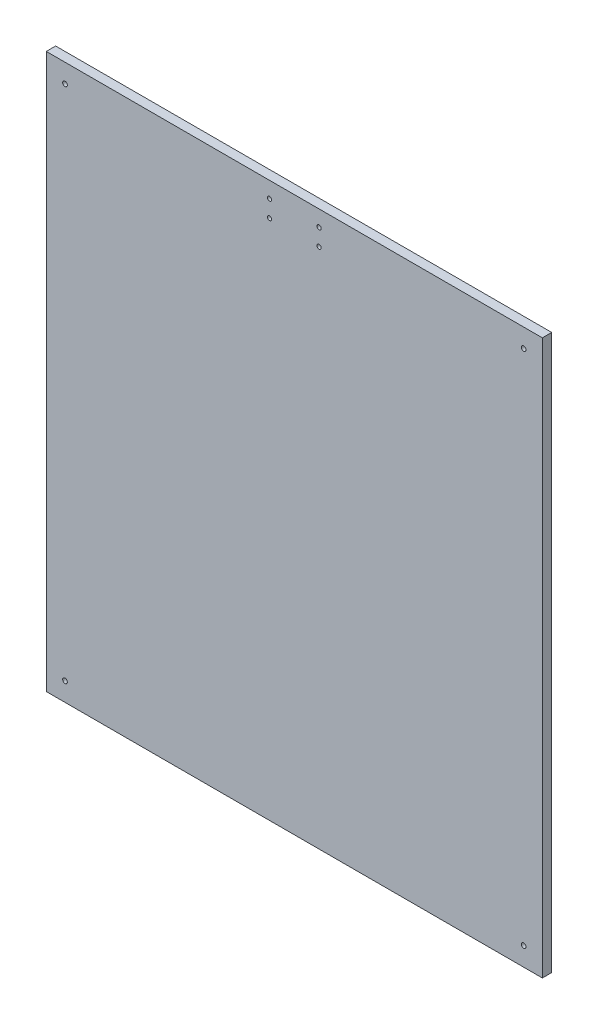
SolidWorks part; units mm, degrees
ref_plane "Спереди" through (0, 0, 0) normal (0, 0, 1) x (1, 0, 0)
ref_plane "Сверху" through (0, 0, 0) normal (0, 1, 0) x (1, 0, 0)
ref_plane "Справа" through (0, 0, 0) normal (1, 0, 0) x (0, 0, -1)
sketch "Эскиз3" plane through (0, 0, 0) normal (0, 0, 1) x (1, 0, 0)
  line L5 (265, -296.15) -> (-265, -296.15)
  line L6 (265, -296.15) -> (265, 296.15)
  line L7 (265, 296.15) -> (-265, 296.15)
  line L8 (-265, -296.15) -> (-265, 296.15)
  point P0 (0, 0)
  point P5 (-265, 0)
  point P6 (0, 296.15)
  dimension "D1" = 592.3
  dimension "D2" = 530
extrude "Бобышка-Вытянуть1" add sketch "Эскиз3" along normal blind 10
sketch "Эскиз4" plane through (0, 0, 10) normal (0, 0, 1) x (1, 0, 0)
  line L0 (265, 296.15) -> (-265, 296.15) construction
  line L1 (-265, 296.15) -> (-265, -296.15) construction
  circle A0 centre (-245, 276.15) radius 2.5
  dimension "D1" = 5
  dimension "D2" = 20
  dimension "D3" = 20
extrude "Вырез-Вытянуть1" cut sketch "Эскиз4" against normal through all contours A0
pattern_linear "Линейный массив1" count 2 spacing 490 along (1, 0, 0) count 2 spacing 552.3 along (0, -1, 0) of "Вырез-Вытянуть1"
sketch "Эскиз7" plane through (0, 0, 0) normal (0, 0, -1) x (-1, 0, 0)
  line L9 (-26.5, 279.15) -> (26.5, 279.15) construction
  line L10 (-26.5, 279.15) -> (-26.5, 261.15) construction
  line L11 (-26.5, 261.15) -> (26.5, 261.15) construction
  line L16 (26.5, 279.15) -> (26.5, 261.15) construction
  line L17 (-265, 296.15) -> (265, 296.15) construction
  circle A0 centre (-26.5, 279.15) radius 2.25
  circle A1 centre (26.5, 279.15) radius 2.25
  circle A2 centre (-26.5, 261.15) radius 2.25
  circle A3 centre (26.5, 261.15) radius 2.25
  point P4 (0, 261.15)
  dimension "D4" = 4.5
  dimension "D5" = 4.5
  dimension "D6" = 4.5
  dimension "D7" = 4.5
  dimension "D1" = 53
  dimension "D2" = 18
  dimension "D3" = 17
extrude "Вырез-Вытянуть2" cut sketch "Эскиз7" against normal through all
equation "\"Ширина груза\"= 420"
equation "\"Глубина груза\"= 490"
equation "\"Высота груза\"= 297"
equation "\"Ширина ячейки\"= \"Ширина груза\" + 10"
equation "\"Глубина ячейки\"= \"Глубина груза\" + 10"
equation "\"Высота ячейки\"= \"Высота груза\" + 10 + 13"
equation "\"Колво ячеек ширина\"= 2"
equation "\"Колво ячеек высота\"= 2"
equation "\"Толщина стенки\"= 10"
equation "\"Крепление дверцы\"= 5"
equation "\"Ширина рейки\"= \"Толщина шестерни\""
equation "\"Высота рейки\"= 20"
equation "\"Высота пола\"= 20"
equation "\"Колво полозьев\"= 5"
equation "\"Отступ рейки\"= 20"
equation "\"Глубина каретки\"= \"Глубина ячейки\" + 30 + \"Мотор Y высота корпуса\" + 20"
equation "\"Длинна рейки\"= ( \"Ширина ячейки\" + \"Толщина стенки\" + \"Крепление дверцы\" ) * \"Колво ячеек ширина\" + \"Ширина ячейки выгрузки\" * \"Колво выгрузки\" + \"Толщина стенки\""
equation "\"Отступ шпильки\"= 20"
equation "\"Диаметр шпильки\"= 5"
equation "\"D1@Бобышка-Вытянуть1\" = \"Толщина стенки\""
equation "\"D1@Эскиз4\"= \"Диаметр шпильки\""
equation "\"D2@Эскиз4\"=\"Отступ шпильки\""
equation "\"D3@Эскиз4\"= \"Отступ шпильки\""
equation "\"D2@Эскиз3\"=\"Ширина ячейки\" + \"Ширина пластины\" * 2"
equation "\"D1@Эскиз3\"=\"Глубина каретки\" "
equation "\"D3@Линейный массив1\"=\"Ширина ячейки\"  +\"Ширина пластины\" *2 - \"Отступ шпильки\" * 2"
equation "\"D4@Линейный массив1\"=\"Глубина каретки\" + \"Ширина рейки\" * 2 - \"Отступ шпильки\" * 2 - \"Ширина рейки\" * 2"
equation "\"Длинна шпильки\"= ( \"Высота ячейки\" + \"Толщина стенки\" + \"Высота пола\" ) * \"Колво ячеек высота\" + ( \"Толщина стенки\" + \"Отступ рейки\" ) * 2 "
equation "\"Ширина пластины\"= 50  "
equation "\"Высота зона выгрузки\"= \"Высота ячейки\" * 2 + \"Толщина стенки\" * 2"
equation "\"Колво выгрузки\"= 1"
equation "\"Отступ крепления мотора фиксации\" = 30"
equation "\"Мотор X ширина корпуса\"= 42.3"
equation "\"Мотор X высота корпуса\"= 42.3"
equation "\"Мотор X длина корпуса\"= 40"
equation "\"Мотор X вылет вала\"= 19.8"
equation "\"Мотор Y ширина корпуса\"= 42.3"
equation "\"Мотор Y высота корпуса\"= 42.3"
equation "\"Мотор Y длина корпуса\"= 48"
equation "\"Мотор Y вылет вала\"= 30"
equation "\"Мотор Z ширина корпуса\"= 42"
equation "\"Мотор Z высота корпуса\"= 42"
equation "\"Мотор Z длина корпуса\"= 40"
equation "\"Мотор Z вылет вала\"= 23"
equation "\"Мотор диаметр вала ПРЕДВ\"= 5"
equation "\"Мотор шаг крепления ПРЕДВ\"= 31"
equation "\"Мотор диаметр отверстий ПРЕДВ\"= 3"
equation "\"Мотор глубина отверстий ПРЕДВ\"= 4.5"
equation "\"Мотор диаметр буртика ПРЕДВ\"= 22"
equation "\"Мотор высота буртика ПРЕДВ\"= 2"
equation "\"Мотор диаметр шкива ПРЕДВ\"= 16"
equation "\"Мотор длина шкива ПРЕДВ\"= 12"
equation "\"Мотор отступ шкива ПРЕДВ\"= 5"
equation "\"Мотор X шаг градусов\"= 1.8"
equation "\"Мотор Y шаг градусов\"= 1.8"
equation "\"Мотор Z шаг градусов\"= 1.8"
equation "\"Мотор Y диаметр ротора\"= 25.78"
equation "\"Толщина шестерни\"= 10"
equation "\"Ширина ячейки выгрузки\"= \"Ширина ячейки\" + \"Толщина стенки\" + \"Отступ крепления мотора фиксации\"*2"
